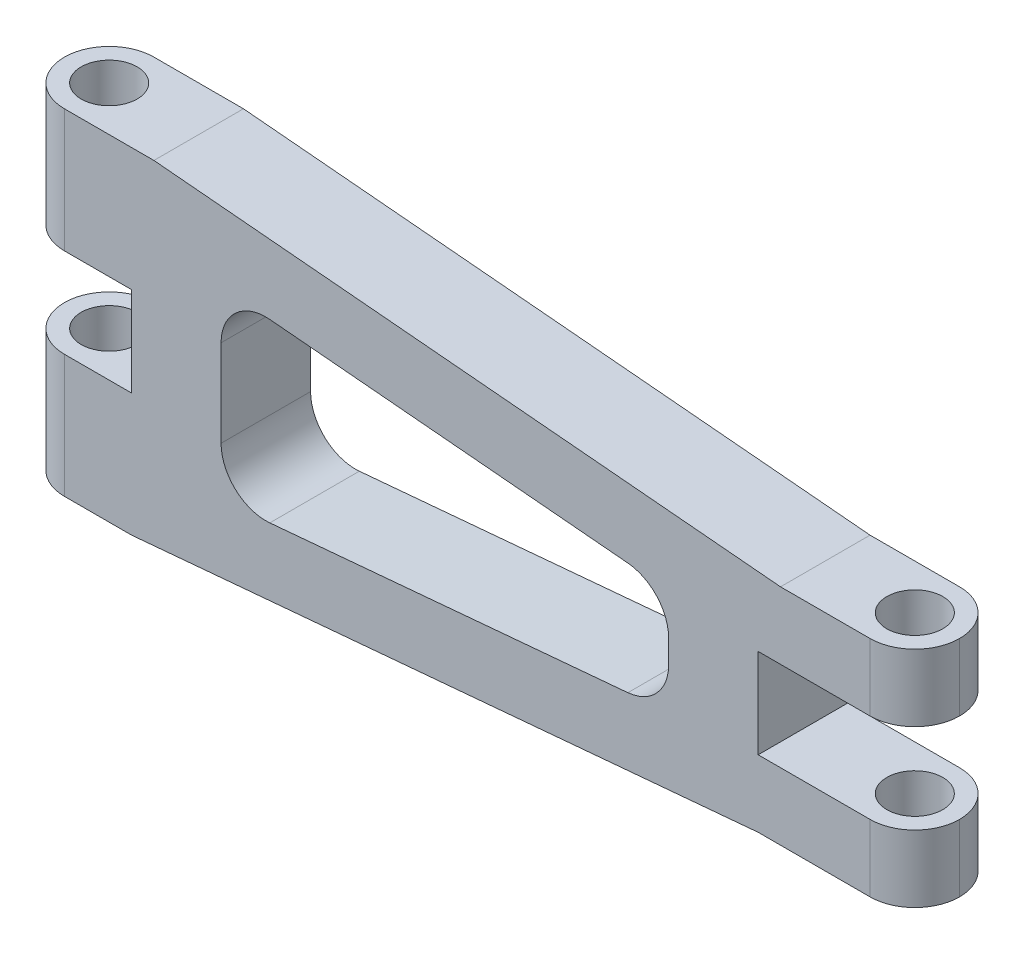
SolidWorks part; units mm, degrees
ref_plane "Plane1" through (0, 0, 0) normal (0, 0, 1) x (1, 0, 0)
ref_plane "Plane2" through (0, 0, 0) normal (0, 1, 0) x (1, 0, 0)
ref_plane "Plane3" through (0, 0, 0) normal (1, 0, 0) x (0, 0, -1)
other "Configuration Table"
sketch "Sketch1" plane through (0, 0, 0) normal (0, 0, 1) x (1, 0, 0)
  line L0 (145.3514, 25) -> (5.3514, 37.5)
  line L2 (120.3539, 11.726) -> (20.3539, 20.6546)
  line L3 (0, 0) -> (110, 0) construction
  line L4 (140.3539, -25) -> (0.3539, -37.5)
  line L5 (120.3539, -11.726) -> (20.3539, -20.6546)
  line L6 (120.3539, -11.726) -> (120.3539, 11.726)
  line L8 (-24.6461, 10) -> (0.3539, 10)
  line L9 (20.3539, 20.6546) -> (20.3539, -20.6546)
  line L10 (175.3539, 25) -> (175.3539, 10)
  line L11 (-24.6461, 37.5) -> (-24.6461, 10)
  line L12 (0.3539, -37.5) -> (-24.6461, -37.5)
  line L13 (5.3514, 37.5) -> (-24.6461, 37.5)
  line L14 (145.3514, 25) -> (175.3539, 25)
  line L15 (140.3539, -25) -> (175.3539, -25)
  line L16 (175.3539, -10) -> (175.3539, -25)
  line L17 (0.3539, -10) -> (-24.6461, -10)
  line L18 (0.3539, -10) -> (0.3539, 10)
  line L19 (175.3539, 10) -> (140.3539, 10)
  line L21 (140.3539, -10) -> (175.3539, -10)
  line L22 (140.3539, -10) -> (140.3539, 10)
  line L23 (-24.6461, -10) -> (-24.6461, -37.5)
  point P0 (140.3539, 0)
  dimension "D1" = 200
  dimension "D2" = 50
  dimension "D3" = 20
  dimension "D4" = 75
  dimension "D5" = 20
  dimension "D6" = 35
  dimension "D7" = 25
  dimension "D8" = 15
  dimension "D9" = 20
  dimension "D10" = 20
extrude "Base-Extrude" add sketch "Sketch1" along normal blind 20
fillet "Fillet1" radius 10 8 edges at (-24.6461, 23.75, 0) (-24.6461, 23.75, 20) (-24.6461, -23.75, 20) (-24.6461, -23.75, 0) (175.3539, 17.5, 0) (175.3539, 17.5, 20) (175.3539, -17.5, 20) (175.3539, -17.5, 0)
fillet "Fillet2" radius 10 4 edges at (20.3539, 20.6546, 10) (20.3539, -20.6546, 10) (120.3539, 11.726, 10) (120.3539, -11.726, 10)
sketch "Sketch4" plane through (0, 0, 0) normal (0, 1, 0) x (1, 0, 0)
  circle A0 centre (165.3539, -10) radius 6.25
  circle A1 centre (-14.6461, -10) radius 6.25
  arc A2 (165.3539, -20) -> (175.3539, -10) centre (165.3539, -10) ccw construction
  arc A3 (-14.6461, 0) -> (-24.6461, -10) centre (-14.6461, -10) ccw construction
  dimension "D1" = 12.5
  dimension "D2" = 12.5
extrude "Cut-Extrude1" cut sketch "Sketch4" against normal through all and the other way through all
